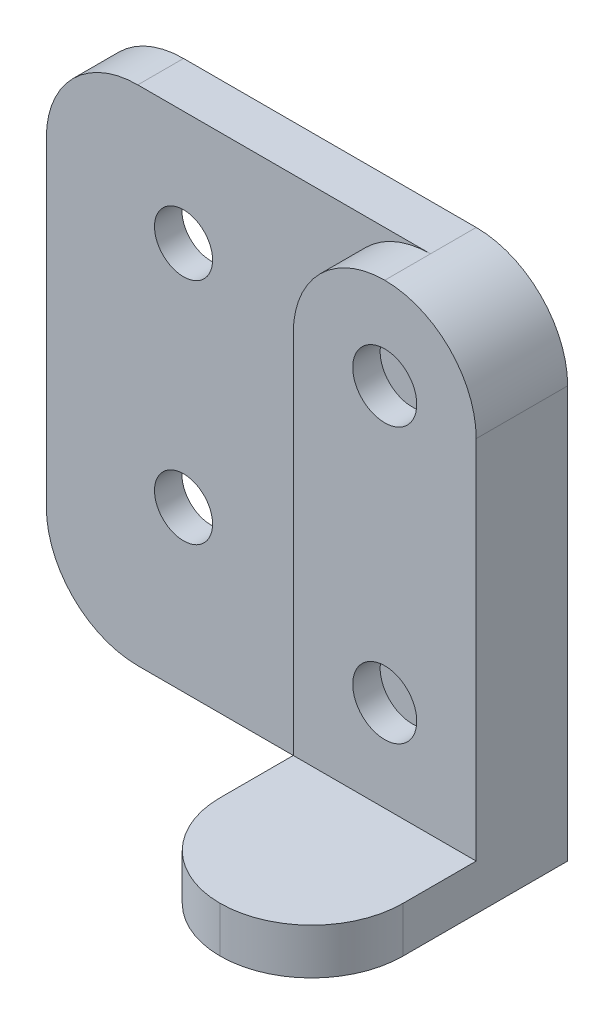
SolidWorks part; units mm, degrees
ref_plane "Front" through (0, 0, 0) normal (0, 0, 1) x (1, 0, 0)
ref_plane "Top" through (0, 0, 0) normal (0, 1, 0) x (1, 0, 0)
ref_plane "Right" through (0, 0, 0) normal (1, 0, 0) x (0, 0, -1)
sketch "Sketch1" plane through (0, 0, 0) normal (0, 0, 1) x (1, 0, 0)
  line L1 (-15, -25) -> (15, -25)
  line L2 (-15, -25) -> (-15, 25)
  line L3 (-15, 25) -> (15, 25)
  line L4 (15, -25) -> (15, 25)
  line L5 (-15, -25) -> (15, 25) construction
  line L6 (-15, 25) -> (15, -25) construction
  point P0 (0, 0)
  dimension "D1" = 50
  dimension "D2" = 30
extrude "Boss-Extrude1" add sketch "Sketch1" along normal blind 5
sketch "Sketch5" plane through (0, 0, 5) normal (0, 0, 1) x (1, 0, 0)
  line L0 (0, -12.5) -> (0, 12.5) construction
  circle A0 centre (0, 12.5) radius 3.175
  circle A1 centre (0, -12.5) radius 3.175
  point P4 (0, 0)
  dimension "D1" = 6.35
  dimension "D2" = 25
extrude "Cut-Extrude2" cut sketch "Sketch5" against normal through all
sketch "Sketch2" plane through (15, 0, 0) normal (1, 0, 0) x (0, 0, -1)
  line L4 (0, -25) -> (0, 25)
  line L5 (0, 25) -> (-5, 25)
  line L6 (-5, 25) -> (-5, -25)
  line L7 (-5, -25) -> (0, -25)
  line L8 (0, -25) -> (0, 25)
  line L9 (0, 25) -> (-5, 25)
  line L10 (-5, 25) -> (-5, -25)
  line L11 (-5, -25) -> (0, -25)
  dimension "D1" = 0
extrude "Boss-Extrude2" add sketch "Sketch2" along normal blind 2
sketch "Sketch3" plane through (17, 0, 0) normal (1, 0, 0) x (0, 0, -1)
  line L0 (-5, -25) -> (0, -25) construction
  line L1 (0, 25) -> (-10, 25)
  line L2 (0, 25) -> (0, -25)
  line L3 (0, -25) -> (-10, -25)
  line L4 (-10, 25) -> (-10, -25)
  dimension "D1" = 10
extrude "Boss-Extrude3" add sketch "Sketch3" along normal blind 20
sketch "Sketch4" plane through (0, 0, 10) normal (0, 0, 1) x (1, 0, 0)
  line L0 (17, 0) -> (37, 0) construction
  line L1 (17, 25) -> (17, -25) construction
  line L2 (37, 25) -> (37, -25) construction
  line L3 (27, -15) -> (27, 15) construction
  circle A0 centre (27, 15) radius 3.5
  circle A1 centre (27, -15) radius 3.5
  point P9 (27, 0)
  point P12 (37, 0)
  dimension "D1" = 7
  dimension "D2" = 30
extrude "Cut-Extrude1" cut sketch "Sketch4" against normal blind 3
sketch "Sketch6" plane through (0, 0, 0) normal (0, 0, -1) x (-1, 0, 0)
  circle A0 centre (0, 12.5) radius 9
  circle A1 centre (0, -12.5) radius 9
  dimension "D1" = 18
extrude "Cut-Extrude3" cut sketch "Sketch6" against normal blind 2
sketch "Sketch7" plane through (0, -25, 0) normal (0, -1, 0) x (1, 0, 0)
  line L0 (-15, 0) -> (37, 0) construction
  line L1 (37, 0) -> (17, 0)
  line L2 (37, 0) -> (37, 28)
  line L3 (37, 28) -> (17, 28)
  line L4 (17, 0) -> (17, 28)
  line L5 (17, 10) -> (17, 5) construction
  line L7 (17, 0) -> (-15, 0)
  line L8 (17, 0) -> (17, 5)
  line L9 (17, 5) -> (-15, 5)
  line L10 (-15, 0) -> (-15, 5)
  line M5 (-15, 0) -> (37, 0)
  line M6 (37, 0) -> (37, 10)
  line M7 (37, 10) -> (17, 10)
  line M8 (17, 10) -> (17, 5)
  line M9 (17, 5) -> (-15, 5)
  line M10 (-15, 5) -> (-15, 0)
  dimension "D1" = 23
extrude "Boss-Extrude4" add sketch "Sketch7" along normal blind 5 contours L4 M5 M9 M10 | L4 M5 M6 M7 M8 | L4 L2 L3 M7 region at (27, -25, 5) region at (1, -25, 2.5) region at (27, -25, 19)
fillet "Fillet1" radius 10 6 edges at (-15, -30, 2.5) (-15, 25, 2.5) (37, 25, 5) (17, -27.5, 28) (37, -27.5, 28) (17, 25, 7.5)
